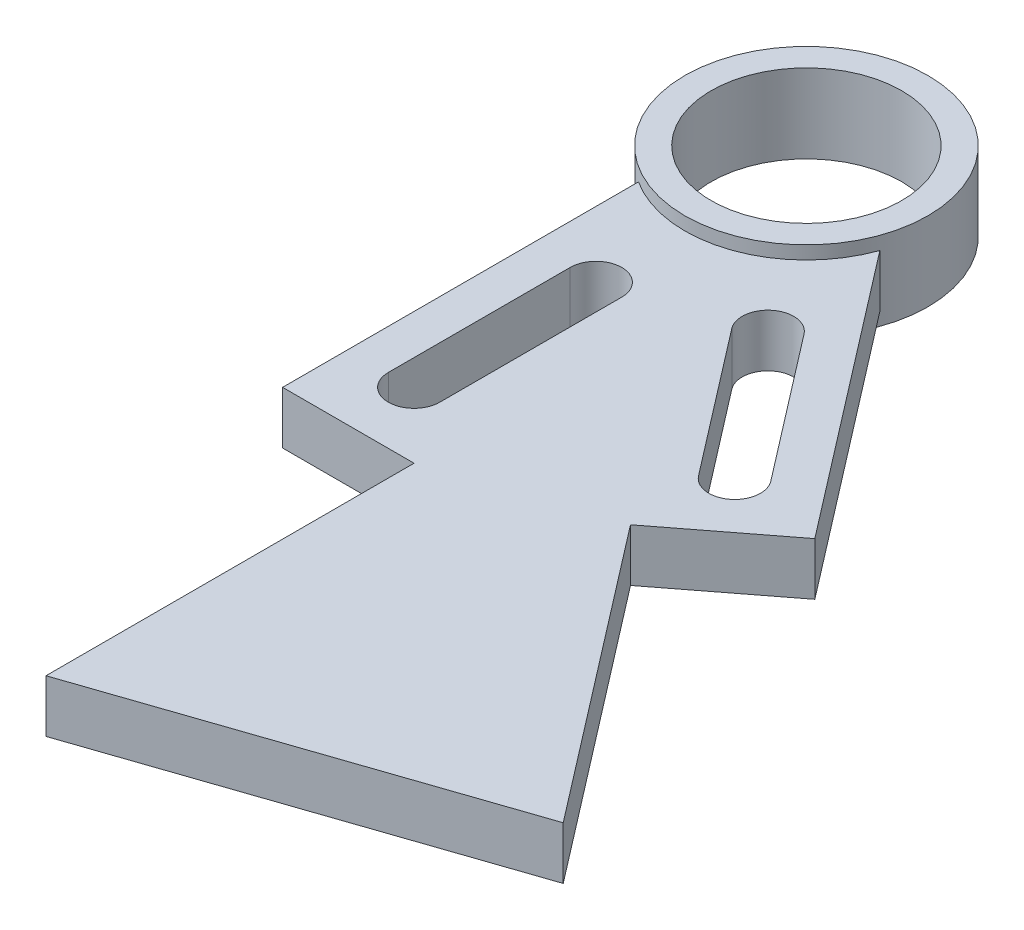
SolidWorks part; units mm, degrees
material "AISI 4130 Steel, normalized at 870C"
ref_plane "Front Plane" through (0, 0, 0) normal (0, 0, 1) x (1, 0, 0)
ref_plane "Top Plane" through (0, 0, 0) normal (0, 1, 0) x (1, 0, 0)
ref_plane "Right Plane" through (0, 0, 0) normal (1, 0, 0) x (0, 0, -1)
sketch "Sketch1" plane through (0, 0, 0) normal (0, 1, 0) x (1, 0, 0)
  line L0 (0, -50.4952) -> (0, -14.6812) construction
  line L1 (30.7905, -40.0214) -> (8.9522, -11.636) construction
  line L2 (0, -47.3837) -> (0, -25.4127) construction
  line L5 (-3.1115, -47.3837) -> (-3.1115, -25.4127)
  line L8 (-7.9375, -55.3212) -> (7.9375, -55.3212)
  line L9 (27.4422, -48.6864) -> (40.0244, -39.0063)
  line L10 (-7.9375, -55.3212) -> (-7.9375, -12.3505)
  line L11 (40.0244, -39.0063) -> (13.822, -4.9486)
  line L12 (7.9375, -55.3212) -> (7.9375, -99.7712)
  line L13 (27.4422, -48.6864) -> (54.5465, -83.9165)
  line L14 (7.9375, -99.7712) -> (54.5465, -83.9165)
  line L15 (0, -14.6812) -> (0, 0) construction
  line L16 (0, -55.3212) -> (0, -50.4952) construction
  line L17 (33.7333, -43.8463) -> (30.7905, -40.0214)
  line L18 (3.1115, -47.3837) -> (3.1115, -25.4127)
  line L19 (15.4959, -20.1415) -> (28.8932, -37.5552) construction
  line L20 (17.962, -18.2442) -> (31.3593, -35.6579)
  line L21 (13.0298, -22.0388) -> (26.4271, -39.4526)
  line L22 (8.9522, -11.636) -> (0, 0) construction
  line L23 (0, 0) -> (21.2677, -62.5217) construction
  line L25 (198.4756, -257.9775) -> (14.2286, -18.4942) construction
  line L27 (0, 0) -> (31.242, -91.8438) construction
  circle A0 centre (0, 0) radius 11.5062
  circle A1 centre (0, 0) radius 14.6812
  arc A2 (-3.1115, -47.3837) -> (3.1115, -47.3837) centre (0, -47.3837) ccw
  arc A3 (3.1115, -25.4127) -> (-3.1115, -25.4127) centre (0, -25.4127) ccw
  arc A4 (17.962, -18.2442) -> (13.0298, -22.0388) centre (15.4959, -20.1415) ccw
  arc A5 (26.4271, -39.4526) -> (31.3593, -35.6579) centre (28.8932, -37.5552) ccw
  point P9 (0, -36.3982)
  point P14 (22.1946, -28.8484)
  point P23 (0, -55.3212)
  point P26 (33.7333, -43.8463)
  point P33 (0, -50.4952)
  point P36 (30.7905, -40.0214)
  point P38 (0, -22.3012)
  dimension "D2" = 29.3624
  dimension "D3" = 40.64
  dimension "D4" = 4.826
  dimension "D6" = 44.45
  dimension "D7" = 7.9375
  dimension "D5" = 4.826
  dimension "D8" = 7.62
  dimension "D9" = 66.04
extrude "Bearing extrude" add sketch "Sketch1" along normal mid plane 9.525 contours A1 A0 region at (-6.8368, 0, -12.521)
extrude "Boss-Extrude2" add sketch "Sketch1<5>" along normal mid plane 6.35 contours A1 L10 L8 L12 L14 L13 L9 L11 A4 A2 region at (18.9901, 0, 55.8263)
sketch "Sketch1<5>" plane through (0, 0, 0) normal (0, 1, 0) x (1, 0, 0) same geometry as "Sketch1"
sketch3d "Tab Point"
  line L0 (21.2677, 0, 62.5217) -> (21.2677, 22.225, 62.5217) construction
  line L1 (0, 0, 0) -> (21.2677, 0, 62.5217) construction
  line L2 (0, 0, 0) -> (31.242, 0, 91.8438) construction
  dimension "D1" = 22.225
equation "\"Apex_thickness\"= .25"
equation "\"Bearing_diameter\"= .906"
equation "\"A-arm_angle\"= 32.91"
equation "\"D1@Sketch1\"=\"Bearing_diameter\""
equation "\"D1@Boss-Extrude2\"= \"Apex_thickness\""
equation "\"apex slot\"= 1.4"
equation "\"tube diameter\"= 5 / 8"
